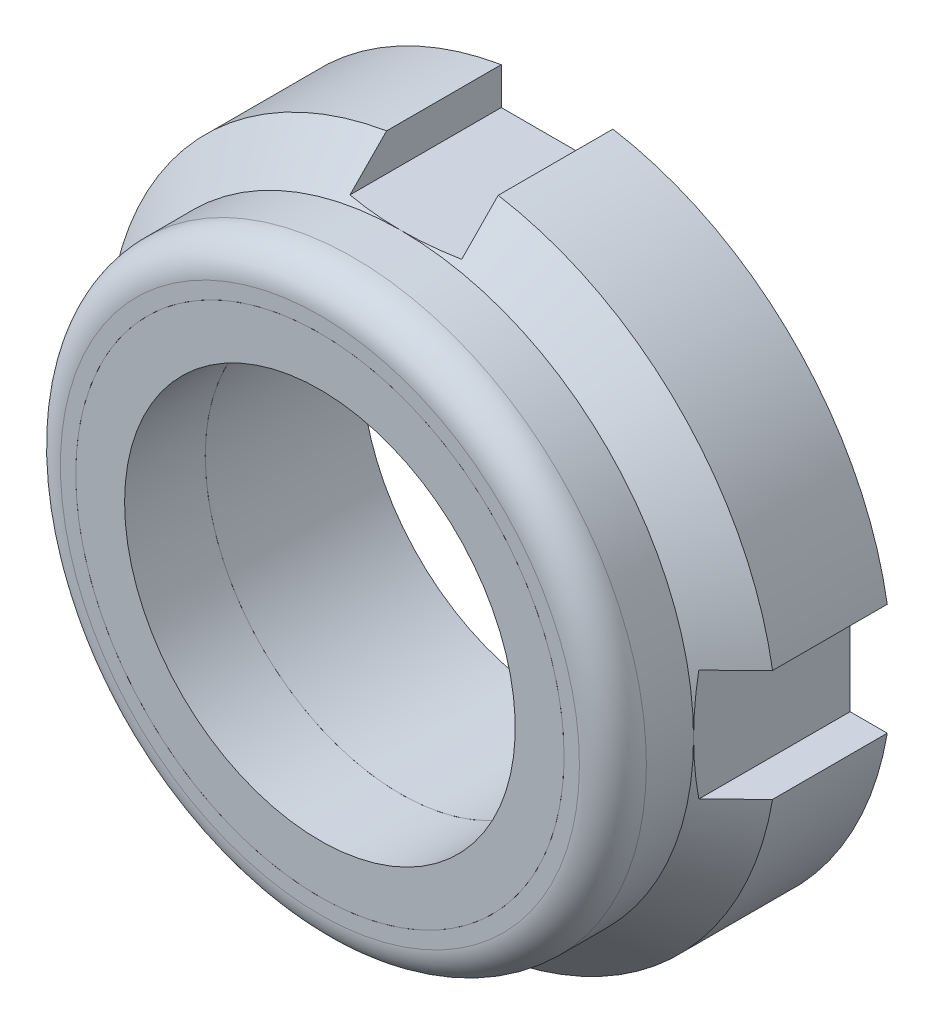
SolidWorks part; units mm, degrees
ref_plane "Front Plane" through (0, 0, 0) normal (0, 0, 1) x (1, 0, 0)
ref_plane "Top Plane" through (0, 0, 0) normal (0, 1, 0) x (1, 0, 0)
ref_plane "Right Plane" through (0, 0, 0) normal (1, 0, 0) x (0, 0, -1)
sketch "Sketch1" plane through (0, 0, 0) normal (0, 0, 1) x (1, 0, 0)
  line L0 (-2, -12) -> (2, -12) construction
  line L1 (0, 0) -> (0, -12) construction
  line L2 (0, 10.5) -> (0, 7) construction
  circle A0 centre (0, 0) radius 12 construction
  circle A1 centre (0, 0) radius 7 construction
  circle A2 centre (0, 0) radius 10.5 construction
  point P9 (0, -10.5)
  point P11 (0, 8.75)
sketch "Sketch2" plane through (0, 0, 0) normal (1, 0, 0) x (0, 0, -1)
  line L0 (-4.25, 0) -> (4.25, 0) construction
  point P2 (0, 0)
  point P3 (-3.75, 0)
  point P5 (-1.36, 0)
  dimension "M" = 5.61
sketch "Sketch4" plane through (0, 0, 0) normal (0, 0, 1) x (1, 0, 0)
  circle A0 centre (0, 0) radius 12 construction
  circle A1 centre (0, 0) radius 12
  circle A2 centre (0, 0) radius 7 construction
  circle A3 centre (0, 0) radius 7
extrude "Boss-Extrude1" add sketch "Sketch4" along normal up to vertex (4.25 mm away) and the other way up to vertex (4.25 mm away) up to point (0, 0, 4.25) other way up to point (0, 0, -4.25)
sketch "Sketch5" plane through (0, 0, 4.25) normal (0, 0, 1) x (1, 0, 0)
  circle A0 centre (0, 0) radius 10.5 construction
  circle A1 centre (0, 0) radius 12
  circle A2 centre (0, 0) radius 12
  circle A3 centre (0, 0) radius 10.5
  dimension "D1" = 0
extrude "Cut-Extrude1" cut sketch "Sketch5" against normal up to vertex (0.5 mm away) up to point (0, 0, 3.75)
sketch "Sketch16" plane through (0, 0, 0) normal (0, 0, 1) x (1, 0, 0)
  line L1 (-2, -10.5) -> (2, -10.5)
  line L2 (-2, -10.5) -> (-2, -12)
  line L3 (-2, -12) -> (2, -12)
  line L4 (2, -10.5) -> (2, -12)
extrude "Cut-Extrude7" cut sketch "Sketch16" against normal through all both and the other way through all
pattern_circular "CirPattern1" count 4 over 360 about axis through (0, 0, 4.25) along (0, 0, -1) of "Cut-Extrude7"
sketch "Sketch18" plane through (0, 0, 0) normal (1, 0, 0) x (0, 0, -1)
  line L0 (-1.36, 10.5) -> (0.14, 12)
  line L2 (0.14, 12) -> (-4.25, 12)
  line L4 (-4.25, 0) -> (4.25, 0) construction
  line L5 (0.14, 12) -> (0, 12) construction
  line L6 (-4.25, 10.5) -> (-1.36, 10.5)
  line L14 (-1.36, 10.5) -> (0, 10.5) construction
  line L22 (-4.25, 10.5) -> (-4.25, -10.5) construction
  line L23 (-4.25, 10.5) -> (-4.25, 12)
  dimension "D1" = 45
revolve "Cut-Revolve1" cut sketch "Sketch18" angle 360 about L4
fillet "Fillet1" radius 1.2 1 edges at (10.5, 0, 4.25)
sketch "Sketch19" plane through (0, 0, 4.25) normal (0, 0, 1) x (1, 0, 0)
  circle A1 centre (0, 0) radius 8.75
extrude "Cut-Extrude8" cut sketch "Sketch19" against normal up to vertex (2.89 mm away) up to point (0, 10.5, 1.36)
sketch "Sketch20" plane through (0, 0, 1.36) normal (0, 0, 1) x (1, 0, 0)
  circle A0 centre (0, 0) radius 7 construction
  circle A1 centre (0, 0) radius 8.75
  circle A2 centre (0, 0) radius 8.75
  circle A3 centre (0, 0) radius 7
  dimension "D1" = 0
extrude "Boss-Extrude2" add sketch "Sketch20" along normal up to vertex (2.89 mm away) separate body up to point (0, 0, 4.25)
ref_axis "Center Axis 1" through (0, 0, -0.14) along (0, 0, -1)
ref_plane "Contact Plane 1" through (0, 0, 4.25) normal (0, 0, -1) x (-1, 0, 0)
ref_plane "Contact Plane 2" through (0, 0, -4.25) normal (0, 0, -1) x (-1, 0, 0)
sketch "Sketch8" [suppressed] plane through (0, 0, 4.25) normal (0, 0, 1) x (1, 0, 0)
  circle A0 centre (0, 0) radius 7 construction
  circle A1 centre (0, 0) radius 7
curve "Helix/Spiral1" [suppressed] pitch 1 height 9.5 turns 9.5 parameters "Pitch"=1
sketch "Sketch14" [suppressed] plane through (0, 0, 4.25) normal (0, 0, 1) x (1, 0, 0)
  circle A0 centre (0, 0) radius 7 construction
  circle A4 centre (0, 0) radius 7
sketch "Sketch15" [suppressed] plane through (0, 0, -4.25) normal (0, 0, -1) x (-1, 0, 0)
  circle A3 centre (0, 0) radius 7 construction
  circle A4 centre (0, 0) radius 7
sketch "Sketch9" [suppressed] plane through (0, 0, 0) normal (1, 0, 0) x (0, 0, -1)
  line L0 (-5.1827, 7.1) -> (-5.125, 7)
  line L1 (-5.125, 7) -> (-4.75, 6.3505)
  line L2 (-4.75, 6.3505) -> (-4.625, 6.3505)
  line L3 (-4.625, 6.3505) -> (-4.25, 7)
  line L4 (-4.25, 7) -> (-4.1923, 7.1)
  line L5 (-4.1923, 7.1) -> (-5.1827, 7.1)
  line L6 (-4.6875, 7.1) -> (-4.6875, 6.3505) construction
  line L7 (-5.125, 7) -> (-4.25, 7) construction
  line L8 (-4.9375, 6.6752) -> (-4.4375, 6.6752) construction
  dimension "D1" = 60
  dimension "D2" = 0.1
  dimension "D3" = 0.125
  dimension "D4" = 0.5
sweep "Sweep1" [suppressed] add profiles "Sketch9" path "Helix/Spiral1"
split "Split5" [suppressed] bodies to split 108
split "Split1" [suppressed] bodies to split 127 125
split "Split2" [suppressed] bodies to split 128 125
combine bodies "Combine1" [suppressed] operation type add bodies to combine 110 126
combine bodies "Combine2" [suppressed] operation type add bodies to combine 113 125
extrude "Cut-Extrude5" [suppressed] cut sketch "Sketch14" against normal up to next draft 60
extrude "Cut-Extrude6" [suppressed] cut sketch "Sketch15" against normal up to next draft 60
equation "\"D3@Helix/Spiral1\"=\"Overall Width@Sketch2\"+\"Pitch@Helix/Spiral1\""
equation "\"D3@Sketch9\"=\"Pitch@Helix/Spiral1\"/8"
equation "\"D4@Sketch9\"=\"Pitch@Helix/Spiral1\"/2"
equation "\"M@Sketch2\"=\"Overall Width@Sketch2\"*.66"
equation "\"D1@Fillet1\"=\"OD@Sketch1\"*.05"
